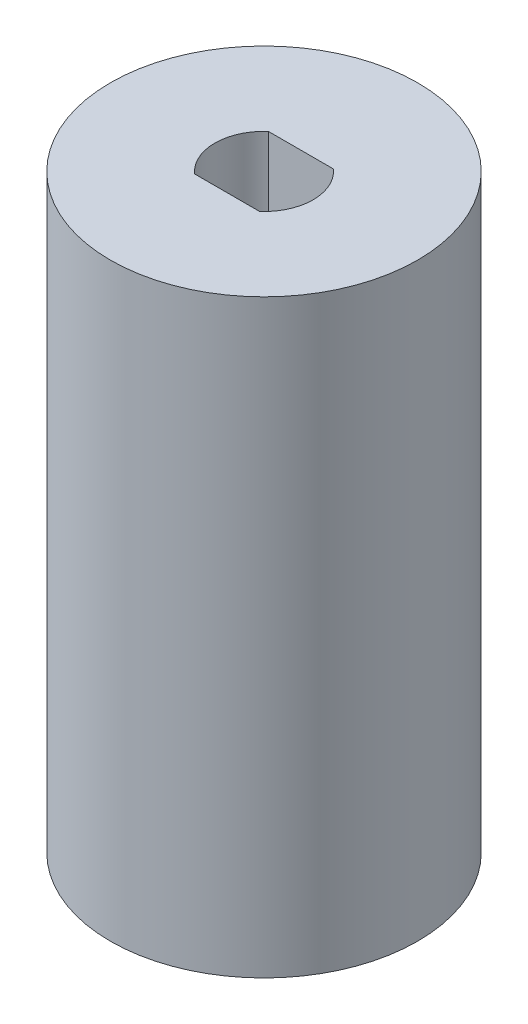
SolidWorks part; units mm, degrees
ref_plane "Alzado" through (0, 0, 0) normal (0, 0, 1) x (1, 0, 0)
ref_plane "Planta" through (0, 0, 0) normal (0, 1, 0) x (1, 0, 0)
ref_plane "Vista lateral" through (0, 0, 0) normal (1, 0, 0) x (0, 0, -1)
sketch "Croquis1" plane through (0, 0, 0) normal (0, 1, 0) x (1, 0, 0)
  circle A0 centre (0, 0) radius 12.5
  dimension "D1" = 25
extrude "Saliente-Extruir1" add sketch "Croquis1" along normal blind 48
sketch "Croquis2" plane through (0, 0, 0) normal (0, 1, 0) x (1, 0, 0)
  line L3 (-2.6458, -3) -> (2.6458, -3)
  line L5 (-2.6458, 3) -> (2.6458, 3)
  line L7 (-3.6269, -1.6869) -> (3.6269, 1.6869) construction
  line L8 (-3.6269, 1.6869) -> (3.6269, -1.6869) construction
  arc A2 (-2.6458, 3) -> (-2.6458, -3) centre (0, 0) ccw
  arc A3 (2.6458, -3) -> (2.6458, 3) centre (0, 0) ccw
  dimension "D1" = 8
extrude "Cortar-Extruir1" cut sketch "Croquis2" along normal blind 15
extrude "Cortar-Extruir2" cut sketch "Croquis2<2>" along normal blind 15 from offset 33
sketch "Croquis2<2>" plane through (0, 0, 0) normal (0, 1, 0) x (1, 0, 0) same geometry as "Croquis2"
